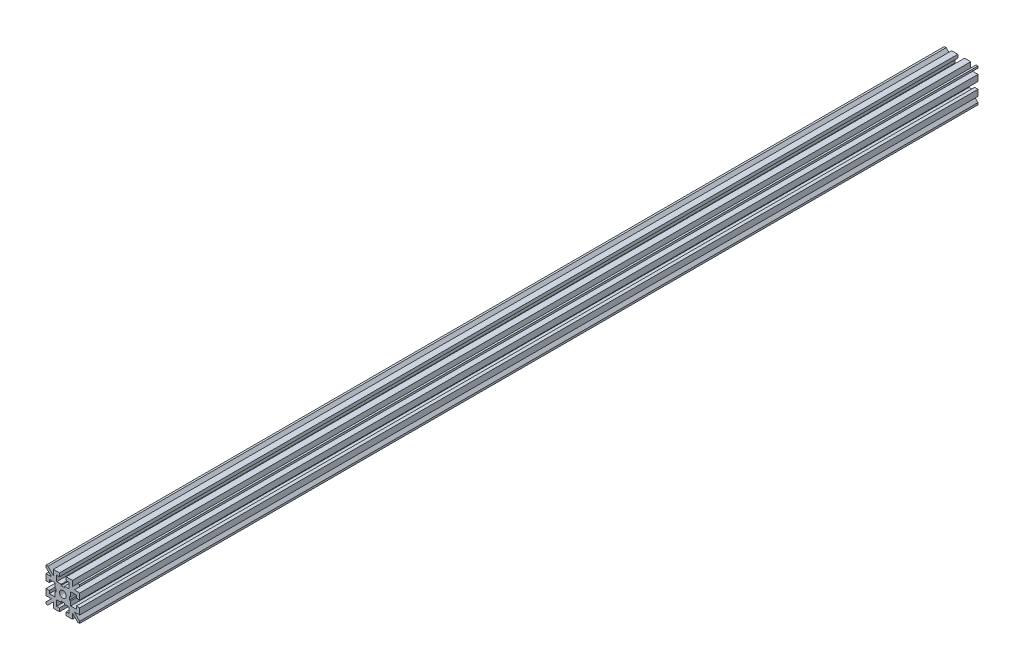
SolidWorks part; units mm, degrees
ref_plane "Front Plane" through (0, 0, 0) normal (0, 0, 1) x (1, 0, 0)
ref_plane "Top Plane" through (0, 0, 0) normal (0, 1, 0) x (1, 0, 0)
ref_plane "Right Plane" through (0, 0, 0) normal (1, 0, 0) x (0, 0, -1)
sketch "Sketch1" plane through (0, 0, 0) normal (0, 0, 1) x (1, 0, 0)
  line L1 (-9.0006, 3.7616) -> (5.9994, 3.7616)
  line L2 (-9.0006, 3.7616) -> (-9.0006, -11.2384)
  line L3 (-9.0006, -11.2384) -> (5.9994, -11.2384)
  line L4 (5.9994, 3.7616) -> (5.9994, -11.2384)
  dimension "D1" = 15
  dimension "D2" = 15
extrude "Boss-Extrude1" add sketch "Sketch1" along normal blind 400
sketch "Sketch2" plane through (0, 0, 400) normal (0, 0, 1) x (1, 0, 0)
  line L0 (-9.0006, 3.7616) -> (5.9994, -11.2384) construction
  line L1 (5.9994, 3.7616) -> (-9.0006, -11.2384) construction
  line L4 (1.9994, -4.4884) -> (1.9994, -6.4884)
  line L5 (5.9994, -3.7384) -> (1.9994, -3.7384) construction
  line L6 (5.9994, -11.2384) -> (5.9994, 3.7616) construction
  line L7 (-1.5006, 3.7616) -> (-1.5006, -3.7384) construction
  line L8 (5.9994, 3.7616) -> (-9.0006, 3.7616) construction
  line L9 (-9.0006, -3.7384) -> (-1.5006, -3.7384) construction
  line L10 (-9.0006, 3.7616) -> (-9.0006, -11.2384) construction
  line L11 (-1.5006, -11.2384) -> (-1.5006, -3.7384) construction
  line L12 (-9.0006, -11.2384) -> (5.9994, -11.2384) construction
  line L13 (1.9994, -4.4884) -> (1.4994, -4.4884)
  line L14 (1.9994, -0.9884) -> (4.4994, -0.9884)
  line L15 (1.9994, -0.9884) -> (1.9994, -2.9884)
  line L16 (1.9994, -6.4884) -> (4.4994, -6.4884)
  line L17 (4.4994, -0.9884) -> (4.4994, -6.4884)
  line L18 (-4.2506, -7.2384) -> (-4.2506, -9.7384)
  line L19 (1.9994, -2.9884) -> (1.4994, -2.9884)
  line L20 (1.4994, -4.4884) -> (1.4994, -2.9884)
  line L21 (1.4994, -3.7384) -> (-0.0006, -3.7384) construction
  line L22 (-2.2506, -7.2384) -> (-4.2506, -7.2384)
  line L23 (-2.2506, -7.2384) -> (-2.2506, -6.7384)
  line L24 (-2.2506, -6.7384) -> (-0.7506, -6.7384)
  line L25 (-0.7506, -7.2384) -> (-0.7506, -6.7384)
  line L26 (1.2494, -7.2384) -> (-0.7506, -7.2384)
  line L27 (1.2494, -7.2384) -> (1.2494, -9.7384)
  line L28 (1.2494, -9.7384) -> (-4.2506, -9.7384)
  line L29 (-5.0006, -0.9884) -> (-7.5006, -0.9884)
  line L30 (-5.0006, -2.9884) -> (-5.0006, -0.9884)
  line L31 (-5.0006, -2.9884) -> (-4.5006, -2.9884)
  line L32 (-4.5006, -2.9884) -> (-4.5006, -4.4884)
  line L33 (-5.0006, -4.4884) -> (-4.5006, -4.4884)
  line L34 (-5.0006, -6.4884) -> (-5.0006, -4.4884)
  line L35 (-5.0006, -6.4884) -> (-7.5006, -6.4884)
  line L36 (-7.5006, -6.4884) -> (-7.5006, -0.9884)
  line L37 (1.2494, -0.2384) -> (1.2494, 2.2616)
  line L38 (-0.7506, -0.2384) -> (1.2494, -0.2384)
  line L39 (-0.7506, -0.2384) -> (-0.7506, -0.7384)
  line L40 (-0.7506, -0.7384) -> (-2.2506, -0.7384)
  line L41 (-2.2506, -0.2384) -> (-2.2506, -0.7384)
  line L42 (-4.2506, -0.2384) -> (-2.2506, -0.2384)
  line L43 (-4.2506, -0.2384) -> (-4.2506, 2.2616)
  line L44 (-4.2506, 2.2616) -> (1.2494, 2.2616)
  circle A0 centre (-1.5006, -3.7384) radius 1.5
  point P60 (-1.5006, -3.7384)
  dimension "D1" = 5.5
  dimension "D2" = 2.5
  dimension "D3" = 1.5
  dimension "D4" = 2.75
  dimension "D5" = 0.5
  dimension "D6" = 1.5
  dimension "D7" = 0.75
  dimension "D8" = 4
extrude "Cut-Extrude1" cut sketch "Sketch2" against normal up to surface (400 mm away) up to face at (-1.5006, -3.7384, 0)
sketch "Sketch3" plane through (0, 0, 400) normal (0, 0, 1) x (1, 0, 0)
  line L0 (5.9994, 3.7616) -> (-9.0006, -11.2384) construction
  line L1 (-9.0006, 3.7616) -> (5.9994, -11.2384) construction
  line L2 (5.1509, 3.7616) -> (2.7494, 1.3602)
  line L3 (5.9994, 3.7616) -> (-9.0006, 3.7616) construction
  line L4 (2.7494, 1.3602) -> (2.7494, 3.7616)
  line L5 (2.7494, 3.7616) -> (5.1509, 3.7616)
  line L6 (1.2494, -0.2384) -> (1.2494, 2.2616) construction
  line L7 (5.9994, 0.5116) -> (5.9994, 2.9131)
  line L8 (3.5979, 0.5116) -> (5.9994, 0.5116)
  line L9 (5.9994, 2.9131) -> (3.5979, 0.5116)
  line L10 (1.2494, 2.2616) -> (-4.2506, 2.2616) construction
  line L11 (-3.0006, 3.7616) -> (-0.0006, 3.7616)
  line L12 (-3.0006, 3.7616) -> (-3.0006, 2.2616)
  line L13 (-3.0006, 2.2616) -> (-0.0006, 2.2616)
  line L14 (-0.0006, 3.7616) -> (-0.0006, 2.2616)
  line L15 (-2.2506, -0.7384) -> (-0.7506, -0.7384) construction
  line L16 (2.7494, -8.8369) -> (2.7494, -11.2384)
  line L17 (2.7494, -11.2384) -> (5.1509, -11.2384)
  line L18 (5.1509, -11.2384) -> (2.7494, -8.8369)
  line L19 (5.9994, -10.3898) -> (3.5979, -7.9884)
  line L20 (3.5979, -7.9884) -> (5.9994, -7.9884)
  line L21 (5.9994, -7.9884) -> (5.9994, -10.3898)
  line L22 (5.9994, -5.2384) -> (4.4994, -5.2384)
  line L23 (5.9994, -2.2384) -> (5.9994, -5.2384)
  line L24 (5.9994, -2.2384) -> (4.4994, -2.2384)
  line L25 (4.4994, -2.2384) -> (4.4994, -5.2384)
  line L26 (-6.5991, -7.9884) -> (-9.0006, -7.9884)
  line L27 (-9.0006, -7.9884) -> (-9.0006, -10.3898)
  line L28 (-9.0006, -10.3898) -> (-6.5991, -7.9884)
  line L29 (-8.1521, -11.2384) -> (-5.7506, -8.8369)
  line L30 (-5.7506, -8.8369) -> (-5.7506, -11.2384)
  line L31 (-5.7506, -11.2384) -> (-8.1521, -11.2384)
  line L32 (-3.0006, -11.2384) -> (-3.0006, -9.7384)
  line L33 (-0.0006, -11.2384) -> (-3.0006, -11.2384)
  line L34 (-0.0006, -11.2384) -> (-0.0006, -9.7384)
  line L35 (-0.0006, -9.7384) -> (-3.0006, -9.7384)
  line L36 (-5.7506, 1.3602) -> (-5.7506, 3.7616)
  line L37 (-5.7506, 3.7616) -> (-8.1521, 3.7616)
  line L38 (-8.1521, 3.7616) -> (-5.7506, 1.3602)
  line L39 (-9.0006, 2.9131) -> (-6.5991, 0.5116)
  line L40 (-6.5991, 0.5116) -> (-9.0006, 0.5116)
  line L41 (-9.0006, 0.5116) -> (-9.0006, 2.9131)
  line L42 (-9.0006, -2.2384) -> (-7.5006, -2.2384)
  line L43 (-9.0006, -5.2384) -> (-9.0006, -2.2384)
  line L44 (-9.0006, -5.2384) -> (-7.5006, -5.2384)
  line L45 (-7.5006, -5.2384) -> (-7.5006, -2.2384)
  point P24 (-1.5006, -0.7384)
  point P27 (-1.5006, -3.7384)
  point P61 (-1.5006, -3.7384)
  dimension "D1" = 0.6
  dimension "D2" = 1.5
  dimension "D3" = 3
  dimension "D4" = 1.5
  dimension "D5" = 4
extrude "Cut-Extrude2" cut sketch "Sketch3" against normal up to surface (400 mm away) up to face at (-1.5006, 0.2616, 0)
